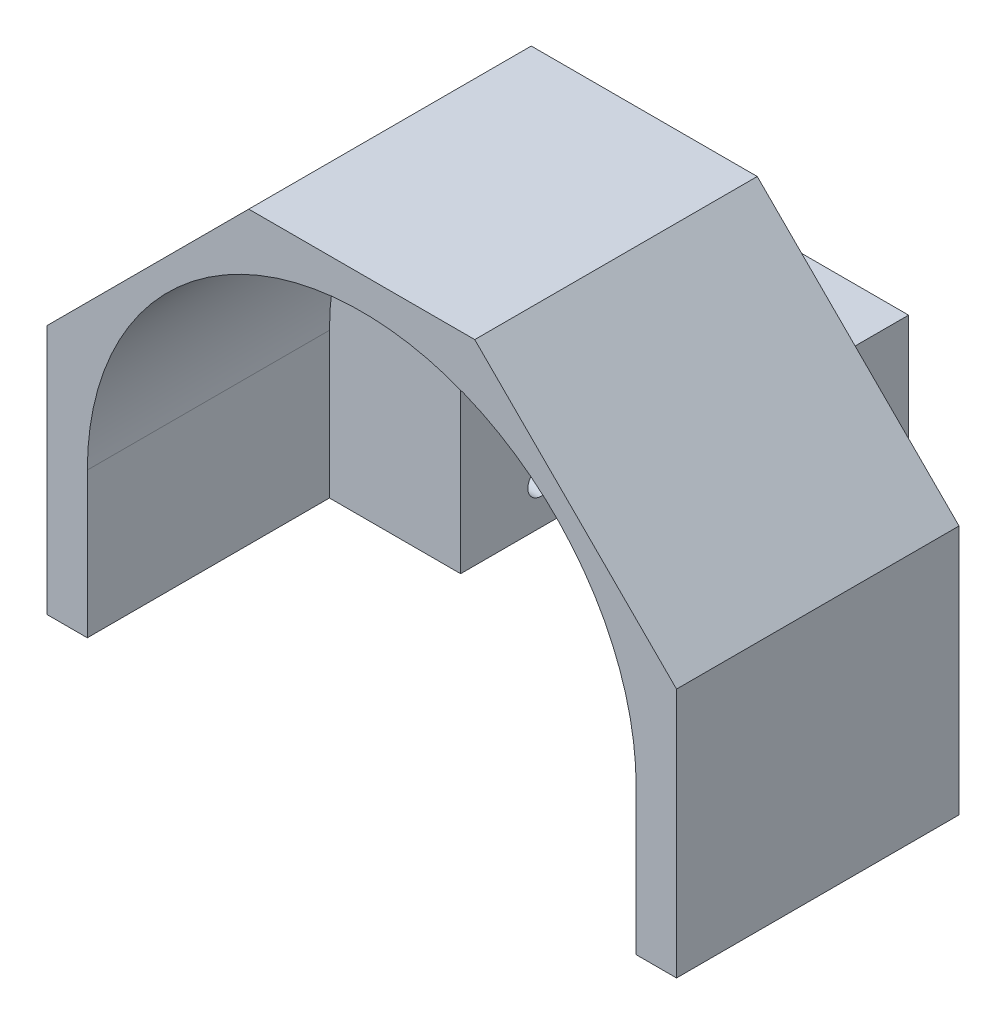
SolidWorks part; units mm, degrees
ref_plane "Plan de face" through (0, 0, 0) normal (0, 0, 1) x (1, 0, 0)
ref_plane "Plan de dessus" through (0, 0, 0) normal (0, 1, 0) x (1, 0, 0)
ref_plane "Plan de droite" through (0, 0, 0) normal (1, 0, 0) x (0, 0, -1)
ref_plane "Plan2" through (0, -10, 0) normal (0, 1, 0) x (1, 0, 0)
sketch "Esquisse3" plane through (0, 0, 0) normal (0, 0, 1) x (1, 0, 0)
  line L1 (-39, 28) -> (39, 28)
  line L2 (-39, 28) -> (-39, -28)
  line L3 (-39, -28) -> (39, -28)
  line L4 (39, 28) -> (39, -28)
  point P4 (0, 28)
  point P5 (-39, 0)
  point P8 (39, 0)
  point P9 (0, -28)
  dimension "D1" = 78
  dimension "D2" = 56
extrude "Boss.-Extru.2" add sketch "Esquisse3" along normal blind 45
sketch "Esquisse4" plane through (0, 0, 45) normal (0, 0, 1) x (1, 0, 0)
  line L2 (39, 28) -> (-39, 28) construction
  line L3 (24.75, -10) -> (-24.75, -10) construction
  circle A0 centre (0, -10) radius 34
  point P2 (0, 28)
  dimension "D1" = 68
extrude "Enlèv. mat.-Extru.1" cut sketch "Esquisse4" against normal blind 30
sketch "Esquisse5" plane through (0, 0, 0) normal (0, 0, -1) x (-1, 0, 0)
  line L0 (39, -28) -> (-39, -28) construction
  line L1 (-17.75, 7.5) -> (17.75, 7.5)
  line L2 (-17.75, 7.5) -> (-17.75, -28)
  line L3 (-17.75, -28) -> (17.75, -28)
  line L4 (17.75, 7.5) -> (17.75, -28)
  point P6 (0, -28)
  dimension "D1" = 35.5
  dimension "D2" = 35.5
extrude "Enlèv. mat.-Extru.2" cut sketch "Esquisse5" against normal up to surface (15 mm away) up to face at (0, -2, 15)
sketch "Esquisse8" plane through (0, 0, 0) normal (0, 0, -1) x (-1, 0, 0)
  line L0 (-22.75, -28) -> (-22.75, 12.5)
  line L1 (-17.75, -28) -> (-39, -28) construction
  line L2 (-22.75, 12.5) -> (22.75, 12.5)
  line L3 (22.75, 12.5) -> (22.75, -28)
  line L4 (39, -28) -> (17.75, -28) construction
  line L5 (22.75, -28) -> (39, -28)
  line L6 (39, -28) -> (39, 28)
  line L7 (39, 28) -> (-39, 28)
  line L8 (-39, 28) -> (-39, -28)
  line L9 (-39, -28) -> (-22.75, -28)
  line L10 (17.75, 7.5) -> (-17.75, 7.5) construction
  line L11 (-17.75, 7.5) -> (-17.75, -28) construction
  line L12 (17.75, -28) -> (17.75, 7.5) construction
  dimension "D1" = 5
  dimension "D2" = 5
  dimension "D3" = 5
extrude "Enlèv. mat.-Extru.5" cut sketch "Esquisse8" against normal blind 10
sketch "Esquisse12" plane through (0, 0, 45) normal (0, 0, 1) x (1, 0, 0)
  line L0 (-39, -28) -> (-28.8444, -28) construction
  line L1 (-34, -28) -> (34, -28)
  line L2 (-34, -28) -> (-34, -10)
  line L3 (-34, -10) -> (34, -10)
  line L4 (34, -28) -> (34, -10)
  line L5 (24.75, -10) -> (-24.75, -10) construction
  arc A0 (28.8444, -28) -> (-28.8444, -28) centre (0, -10) ccw construction
extrude "Enlèv. mat.-Extru.6" cut sketch "Esquisse12" against normal up to surface (30 mm away) up to face at (0, -7.5, 15)
sketch "Esquisse13" plane through (-22.75, 0, 0) normal (-1, 0, 0) x (0, 0, 1)
  line L0 (0, 12.5) -> (0, -28) construction
  line L1 (10, -28) -> (0, -28) construction
  circle A0 centre (5, -23) radius 1.6715
  dimension "D1" = 5
  dimension "D2" = 5
extrude "Enlèv. mat.-Extru.7" cut sketch "Esquisse13" against normal through all
sketch "Esquisse15" plane through (-22.75, 0, 0) normal (-1, 0, 0) x (0, 0, 1)
  line L0 (10, 12.5) -> (0, 12.5) construction
  line L1 (0, 12.5) -> (0, -28) construction
  circle A0 centre (5, 2.5) radius 1.5
  dimension "D1" = 3
  dimension "D2" = 10
  dimension "D3" = 5
extrude "Enlèv. mat.-Extru.8" cut sketch "Esquisse15" against normal through all
sketch "Esquisse16" plane through (0, 0, 15) normal (0, 0, 1) x (1, 0, 0)
  line L0 (-17.75, -28) -> (-17.75, 7.5) construction
  line L1 (-21.75, 3.5) -> (-13.75, 3.5)
  line L2 (-21.75, 3.5) -> (-21.75, 11.5)
  line L3 (-21.75, 11.5) -> (-13.75, 11.5)
  line L4 (-13.75, 3.5) -> (-13.75, 11.5)
  line L6 (-17.75, 7.5) -> (17.75, 7.5) construction
  dimension "D1" = 4
  dimension "D2" = 4
  dimension "D3" = 4
  dimension "D4" = 4
extrude "Enlèv. mat.-Extru.9" cut sketch "Esquisse16" against normal blind 4
sketch "Esquisse17" plane through (0, 12.5, 0) normal (0, 1, 0) x (1, 0, 0)
  line L0 (-22.75, -10) -> (-22.75, 0) construction
  line L1 (22.75, 0) -> (-22.75, 0) construction
  circle A0 centre (-12.75, -5) radius 1.5
  dimension "D1" = 3
  dimension "D2" = 10
  dimension "D3" = 5
extrude "Enlèv. mat.-Extru.10" cut sketch "Esquisse17" against normal through all
sketch "Esquisse18" plane through (0, 12.5, 0) normal (0, 1, 0) x (1, 0, 0)
  line L0 (22.75, -10) -> (22.75, 0) construction
  circle A0 centre (12.75, -5) radius 1.5
  dimension "D1" = 3
  dimension "D2" = 5
  dimension "D3" = 10
extrude "Enlèv. mat.-Extru.11" cut sketch "Esquisse18" against normal through all
sketch "Esquisse19" plane through (0, 0, 15) normal (0, 0, 1) x (1, 0, 0)
  line L0 (17.75, 7.5) -> (17.75, -28) construction
  line L1 (13.75, 11.5) -> (21.75, 11.5)
  line L2 (13.75, 11.5) -> (13.75, 3.5)
  line L3 (13.75, 3.5) -> (21.75, 3.5)
  line L4 (21.75, 11.5) -> (21.75, 3.5)
  line L5 (-13.75, 7.5) -> (17.75, 7.5) construction
  dimension "D1" = 4
  dimension "D2" = 4
  dimension "D3" = 4
  dimension "D4" = 4
extrude "Enlèv. mat.-Extru.12" cut sketch "Esquisse19" against normal blind 4
sketch "Esquisse20" plane through (0, 0, 45) normal (0, 0, 1) x (1, 0, 0)
  line L0 (-39, 3) -> (-39, 28)
  line L2 (-39, 28) -> (-14, 28)
  line L3 (39, 28) -> (-39, 28) construction
  line L4 (-14, 28) -> (-39, 3)
  line L5 (-39, 28) -> (-39, -28) construction
  dimension "D1" = 25
extrude "Enlèv. mat.-Extru.13" cut sketch "Esquisse20" against normal through all
mirror "Symétrie1" about plane through (0, 0, 0) normal (1, 0, 0) of "Enlèv. mat.-Extru.13"
